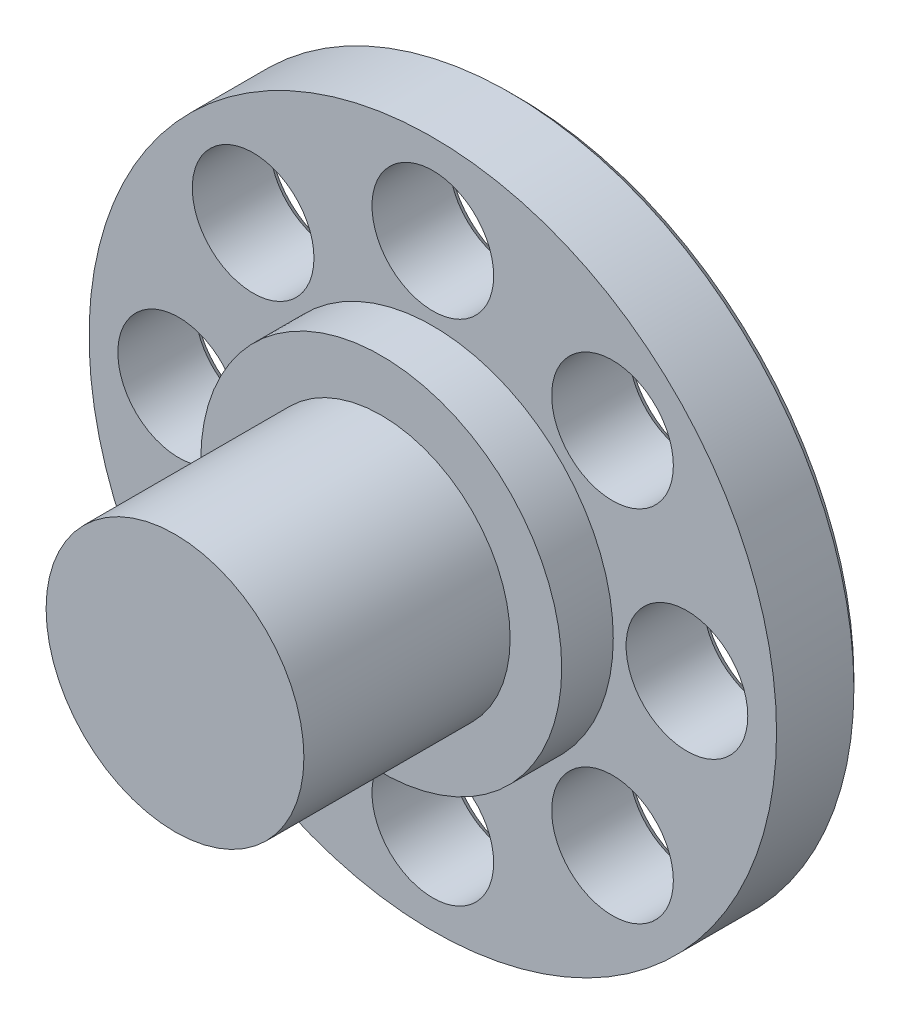
SolidWorks part; units mm, degrees
material "ABS PC"
ref_plane "Front Plane" through (0, 0, 0) normal (0, 0, 1) x (1, 0, 0)
ref_plane "Top Plane" through (0, 0, 0) normal (0, 1, 0) x (1, 0, 0)
ref_plane "Right Plane" through (0, 0, 0) normal (1, 0, 0) x (0, 0, -1)
sketch "Sketch1" plane through (0, 0, 0) normal (0, 0, 1) x (1, 0, 0)
  circle A0 centre (0, 0) radius 20
  circle A2 centre (0, 14.785) radius 3.54
  circle A3 centre (10.4546, 10.4546) radius 3.54
  circle A4 centre (14.785, 0) radius 3.54
  circle A5 centre (10.4546, -10.4546) radius 3.54
  circle A6 centre (0, -14.785) radius 3.54
  circle A7 centre (-10.4546, -10.4546) radius 3.54
  circle A8 centre (-14.785, 0) radius 3.54
  circle A9 centre (-10.4546, 10.4546) radius 3.54
  circle A10 centre (0, 0) radius 9
  point P22 (0, 0)
  dimension "D1" = 40
  dimension "D3" = 7.08
  dimension "D5" = 18
  dimension "D4" = 8
extrude "Boss-Extrude1" add sketch "Sketch1" along normal blind 5
sketch "Sketch2" plane through (0, 0, 5) normal (0, 0, 1) x (1, 0, 0)
  circle A0 centre (0, 0) radius 10.5
  dimension "D1" = 21
extrude "Boss-Extrude2" add sketch "Sketch2" along normal blind 15
sketch "Sketch3" plane through (0, 0, 0) normal (0, 0, -1) x (-1, 0, 0)
  circle A0 centre (0, 0) radius 9
  circle A1 centre (0, 0) radius 5.5
  dimension "D1" = 11
extrude "Boss-Extrude3" add sketch "Sketch3" against normal up to surface (5 mm away) up to face at (9, 0, 5)
chamfer "Chamfer1" distance 0.5 angle 45 10 edges at (-5.5, 0, 0) (-6.9146, 10.4546, 0) (-11.245, 0, 0) (-6.9146, -10.4546, 0) (3.54, -14.785, 0) (13.9946, -10.4546, 0) (18.325, 0, 0) (13.9946, 10.4546, 0) (3.54, 14.785, 0) (20, 0, 0)
sketch "Sketch4" plane through (0, 0, 20) normal (0, 0, 1) x (1, 0, 0)
  circle A0 centre (0, 0) radius 7.5
  circle A1 centre (0, 0) radius 10.5
  dimension "D1" = 15
extrude "Cut-Extrude2" cut sketch "Sketch4" against normal blind 12
sketch "Sketch5" plane through (0, 0, 0) normal (0, 0, -1) x (-1, 0, 0)
  circle A1 centre (0, 0) radius 5.5
  dimension "D1" = 11
extrude "Cut-Extrude3" cut sketch "Sketch5" against normal blind 8
